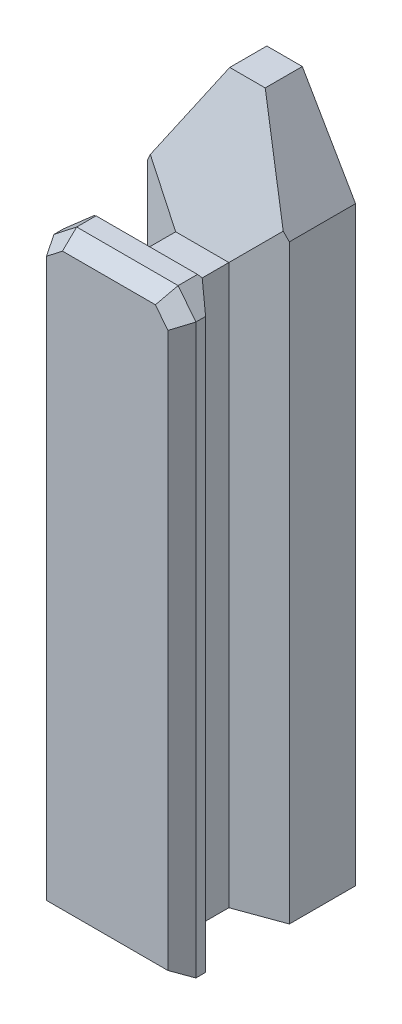
SolidWorks part; units mm, degrees
ref_plane "Front Plane" through (0, 0, 0) normal (0, 0, 1) x (1, 0, 0)
ref_plane "Top Plane" through (0, 0, 0) normal (0, 1, 0) x (1, 0, 0)
ref_plane "Right Plane" through (0, 0, 0) normal (1, 0, 0) x (0, 0, -1)
sketch "Sketch1" plane through (0, 0, 0) normal (0, 0, 1) x (1, 0, 0)
  line L1 (-8, 46) -> (8, 46)
  line L2 (-8, 46) -> (-8, -31)
  line L3 (-8, -31) -> (8, -31)
  line L4 (8, 46) -> (8, -31)
  circle A0 centre (0, 30) radius 1.5
  circle A1 centre (0, -23) radius 1.5
  dimension "D1" = 30
  dimension "D2" = 23
  dimension "D3" = 3
  dimension "D4" = 3
  dimension "D7" = 8
  dimension "D5" = 8
  dimension "D6" = 8
  dimension "D8" = 16
extrude "Boss-Extrude1" add sketch "Sketch1" along normal blind 2
chamfer "Chamfer1" distance 6 angle 60 2 edges at (8, 46, 1) (-8, 46, 1)
sketch "Sketch2" plane through (0, 0, 2) normal (0, 0, 1) x (1, 0, 0)
  line L0 (-8, 35.6077) -> (-8, -31) construction
  line L1 (-3, 32) -> (3, 32)
  line L2 (-3, 32) -> (-3, -31)
  line L3 (-3, -31) -> (3, -31)
  line L4 (3, 32) -> (3, -31)
  line L5 (8, -31) -> (8, 35.6077) construction
  circle A0 centre (0, 30) radius 1.5 construction
  circle A1 centre (0, -23) radius 1.5 construction
  dimension "D1" = 5
  dimension "D2" = 5
  dimension "D3" = 2
  dimension "D4" = 8
extrude "Boss-Extrude2" add sketch "Sketch2" along normal blind 18
chamfer "Chamfer2" distance 20 angle 20 5 edges at (3, 0.5, 2) (5.5, -31, 2) (-5.5, -31, 2) (-3, 0.5, 2) (0, 32, 2)
sketch "Sketch3" plane through (0, 0, 20) normal (0, 0, 1) x (1, 0, 0)
  line L0 (-8, -31) -> (8, -31) construction
  line L1 (-8, 35.6077) -> (8, 35.6077)
  line L2 (-8, 35.6077) -> (-8, -31)
  line L3 (-8, -31) -> (8, -31)
  line L4 (8, 35.6077) -> (8, -31)
  dimension "D1" = 0
extrude "Boss-Extrude3" add sketch "Sketch3" against normal blind 3
chamfer "Chamfer3" distance 4 angle 52 5 edges at (3, 0.5, 17) (5.5, -31, 17) (-5.5, -31, 17) (-3, 0.5, 17) (0, 32, 17)
chamfer "Chamfer4" distance 2 angle 52 2 edges at (8, 35.6077, 18.4532) (-8, 35.6077, 18.4532)
chamfer "Chamfer6" distance 2 angle 30 6 edges at (7, 34.3278, 20) (8, 1.0239, 20) (-8, 1.3038, 20) (-6.7201, 34.6077, 20) (0.2799, 35.6077, 20) (0, -31, 20)
ref_plane "Plane1" through (0, 0, 1.5) normal (0, 0, -1) x (-1, 0, 0)
sketch "Sketch4" plane through (0, 0, 1.5) normal (0, 0, -1) x (-1, 0, 0)
  line L0 (-2, 46) -> (2, 46) construction
  line L1 (1.7032, 32.95) -> (-1.7032, 32.95)
  line L2 (-1.7032, 32.95) -> (-3.4064, 30)
  line L3 (-3.4064, 30) -> (-1.7032, 27.05)
  line L4 (-1.7032, 27.05) -> (1.7032, 27.05)
  line L7 (1.7032, 32.95) -> (10.5507, 32.95)
  line L8 (10.5507, 32.95) -> (10.5507, 27.05)
  line L9 (10.5507, 27.05) -> (1.7032, 27.05)
  line L10 (1.7032, -20.05) -> (-1.7032, -20.05)
  line L11 (6.0189, 34.525) -> (6.8705, 36)
  line L12 (-0.9093, 37.475) -> (-1.7609, 38.95)
  line L13 (-1.7032, -20.05) -> (-3.4064, -23)
  line L14 (-3.4064, -23) -> (-1.7032, -25.95)
  line L15 (-1.7032, -25.95) -> (1.7032, -25.95)
  line L16 (1.7032, -20.05) -> (10.5507, -20.05)
  line L17 (10.5507, -20.05) -> (10.5507, -25.95)
  line L18 (10.5507, -25.95) -> (1.7032, -25.95)
  arc A0 (0.768, 32.8483) -> (1.0755, 32.7469) centre (0, 30) ccw construction
  arc A1 (0.768, -20.1517) -> (1.0755, -20.2531) centre (0, -23) ccw construction
  dimension "D1" = 5.9
  dimension "D2" = 0
  dimension "D3" = 2
  dimension "D4" = 53
extrude "Cut-Extrude1" cut sketch "Sketch4" against normal blind 2.6
ref_plane "Plane2" through (0, -30, 0) normal (0, -1, 0) x (-1, 0, 0)
sketch "Sketch8" plane through (0, -30, 0) normal (0, -1, 0) x (-1, 0, 0)
  line L0 (-4.6, -4.7) -> (-4.6, 0)
  line L1 (8, 0) -> (-8, 0) construction
  line L2 (4.6, -4.7) -> (4.6, 0)
  line L4 (-4.6, 0) -> (4.6, 0)
  line L5 (-8, -7.4596) -> (-8, 0) construction
  arc A0 (-4.6, -4.7) -> (4.6, -4.7) centre (0, -4.7) ccw
  dimension "D1" = 4.7
  dimension "D3" = 8
  dimension "D2" = 9.2
extrude "Cut-Extrude3" cut sketch "Sketch8" against normal blind 3.1
sketch "Sketch9" plane through (0, 0, 0) normal (0, 0, -1) x (-1, 0, 0)
  circle A0 centre (0, 30) radius 1.5
  circle A1 centre (0, -23) radius 1.5
extrude "3" cut sketch "Sketch9" against normal blind 6.5
